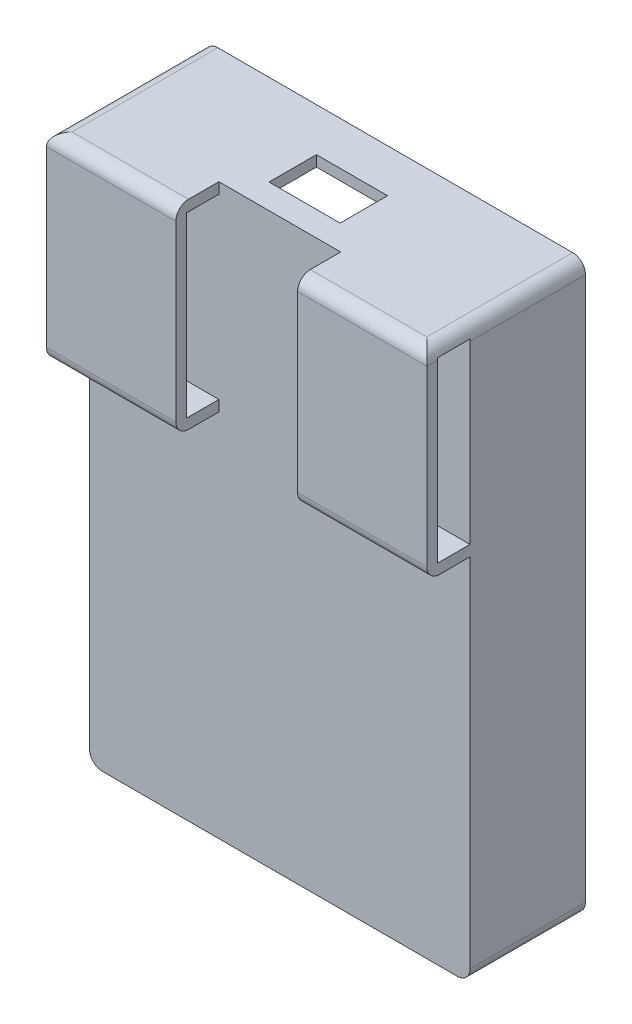
SolidWorks part; units mm, degrees
ref_plane "Front Plane" through (0, 0, 0) normal (0, 0, 1) x (1, 0, 0)
ref_plane "Top Plane" through (0, 0, 0) normal (0, 1, 0) x (1, 0, 0)
ref_plane "Right Plane" through (0, 0, 0) normal (1, 0, 0) x (0, 0, -1)
sketch "Sketch1" plane through (0, 0, 0) normal (0, 1, 0) x (1, 0, 0)
  line L1 (0, 0) -> (89.662, 0)
  line L2 (0, 0) -> (0, 27.225)
  line L3 (0, 27.225) -> (89.662, 27.225)
  line L4 (89.662, 0) -> (89.662, 27.225)
  dimension "D1" = 89.662
  dimension "D2" = 27.225
extrude "Boss-Extrude1" add sketch "Sketch1" along normal blind 87.122
shell "Shell1" thickness 2.54 removed face at (44.831, 43.561, -27.225)
sketch "Sketch12" plane through (0, 87.122, 0) normal (0, 1, 0) x (1, 0, 0)
  line L1 (0, 0) -> (89.662, 0)
  line L2 (0, 0) -> (0, 27.225)
  line L3 (0, 27.225) -> (89.662, 27.225)
  line L4 (89.662, 0) -> (89.662, 27.225)
extrude "Boss-Extrude6" add sketch "Sketch12" along normal blind 46.99
shell "Shell2" thickness 2.54 removed face at (44.831, 67.056, -27.225)
sketch "Sketch5" plane through (0, 88.392, -2.54) normal (0, 0, -1) x (1, 0, 0)
  line L0 (2.54, 1.27) -> (87.122, 1.27) construction
  line L3 (2.54, -43.18) -> (2.54, 1.27) construction
  circle A0 centre (15.24, -29.845) radius 3.175
  circle A1 centre (15.24, -29.845) radius 1.5
  circle A2 centre (15.24, -9.525) radius 3.175
  circle A3 centre (15.24, -9.525) radius 1.5
  circle A4 centre (49.53, -9.525) radius 3.175
  circle A5 centre (49.53, -9.525) radius 1.5
  circle A6 centre (49.53, -29.845) radius 3.175
  circle A7 centre (49.53, -29.845) radius 1.5
  point P12 (0, 0)
  point P16 (14.292, -57.2702)
  dimension "D4" = 6.35
  dimension "D5" = 6.35
  dimension "D6" = 6.35
  dimension "D7" = 6.35
  dimension "D8" = 3
  dimension "D9" = 3
  dimension "D10" = 3
  dimension "D11" = 3
  dimension "D1" = 20.32
  dimension "D2" = 10.795
  dimension "D3" = 34.29
  dimension "D12" = 12.7
extrude "Boss-Extrude7" add sketch "Sketch5" along normal blind 1.905
sketch "Sketch14" plane through (0, 134.112, 0) normal (0, 1, 0) x (1, 0, 0)
  line L0 (0, 27.225) -> (0, 0) construction
  line L1 (53.213, 17.018) -> (36.449, 17.018)
  line L2 (53.213, 17.018) -> (53.213, 5.842)
  line L3 (53.213, 5.842) -> (36.449, 5.842)
  line L4 (36.449, 17.018) -> (36.449, 5.842)
  line L5 (53.213, 17.018) -> (36.449, 5.842) construction
  line L6 (53.213, 5.842) -> (36.449, 17.018) construction
  line L7 (0, 0) -> (89.662, 0) construction
  point P0 (44.831, 11.43)
  dimension "D1" = 16.764
  dimension "D2" = 11.176
  dimension "D3" = 44.831
  dimension "D4" = 11.43
extrude "Cut-Extrude10" cut sketch "Sketch14" against normal up to next
sketch "Sketch15" plane through (0, 0, 0) normal (0, 0, 1) x (1, 0, 0)
  line L1 (0, 134.112) -> (30.48, 134.112)
  line L2 (0, 134.112) -> (0, 87.122)
  line L3 (0, 87.122) -> (30.48, 87.122)
  line L4 (30.48, 134.112) -> (30.48, 87.122)
  line L5 (89.662, 134.112) -> (59.182, 134.112)
  line L6 (89.662, 134.112) -> (89.662, 87.122)
  line L7 (89.662, 87.122) -> (59.182, 87.122)
  line L8 (59.182, 134.112) -> (59.182, 87.122)
  dimension "D1" = 30.48
  dimension "D2" = 30.48
  dimension "D3" = 46.99
  dimension "D4" = 46.99
extrude "Boss-Extrude8" add sketch "Sketch15" along normal blind 10.16
sketch "Sketch16" plane through (0, 0, 0) normal (-1, 0, 0) x (0, 0, 1)
  line L0 (10.16, 134.112) -> (10.16, 87.122) construction
  line L1 (7.62, 89.662) -> (0, 89.662)
  line L2 (7.62, 89.662) -> (7.62, 131.572)
  line L3 (7.62, 131.572) -> (0, 131.572)
  line L4 (0, 89.662) -> (0, 131.572)
  line L5 (10.16, 87.122) -> (0, 87.122) construction
  line L6 (-27.225, 134.112) -> (10.16, 134.112) construction
  line L8 (0, 87.122) -> (0, 0) construction
  dimension "D1" = 2.54
  dimension "D2" = 2.54
  dimension "D3" = 2.54
extrude "Cut-Extrude11" cut sketch "Sketch16" against normal through all
chamfer "Chamfer1" distance 5.08 angle 45 4 edges at (87.122, 2.54, -14.8825) (2.54, 2.54, -14.8825) (2.54, 84.582, -14.8825) (87.122, 84.582, -14.8825)
sketch "Sketch17" plane through (0, 0, -27.225) normal (0, 0, -1) x (-1, 0, 0)
  line L0 (-89.662, 134.112) -> (-89.662, 0) construction
  line L1 (-87.122, 87.122) -> (-2.54, 87.122) construction
  line L2 (0, 134.112) -> (0, 0) construction
  line L3 (-89.662, 0) -> (0, 0) construction
  circle A0 centre (-3, 84.122) radius 1.5
  circle A1 centre (-86.662, 84.122) radius 1.5
  circle A2 centre (-86.662, 3) radius 1.5
  circle A3 centre (-3, 3) radius 1.5
  point P8 (0, 0)
  point P9 (0, 0)
  point P10 (0, 0)
  point P11 (0, 0)
  point P12 (0, 0)
  dimension "D1" = 3
  dimension "D2" = 3
  dimension "D3" = 3
  dimension "D7" = 3
  dimension "D4" = 3
  dimension "D5" = 3
  dimension "D6" = 3
  dimension "D8" = 3
extrude "Cut-Extrude12" cut sketch "Sketch17" against normal blind 10
fillet "Fillet1" radius 3 8 edges at (74.422, 134.112, 10.16) (15.24, 134.112, 10.16) (74.422, 87.122, 10.16) (15.24, 87.122, 10.16) (89.662, 134.112, -8.5325) (89.662, 0, -13.6125) (0, 0, -13.6125) (0, 134.112, -8.5325)
